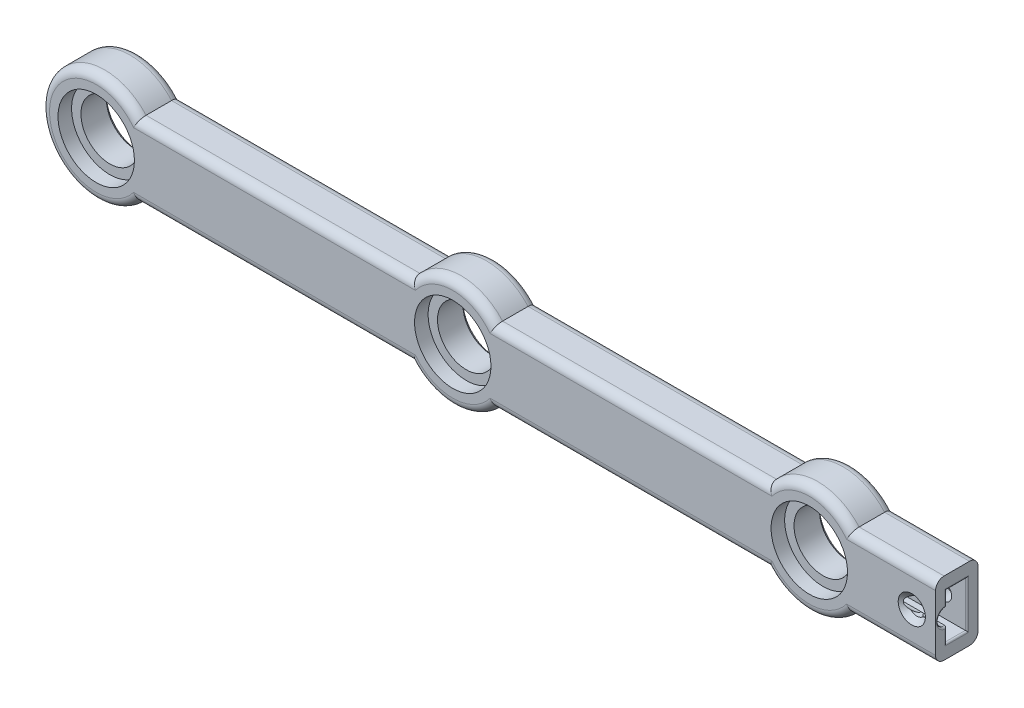
SolidWorks part; units mm, degrees
material "ABS"
ref_plane "Front Plane" through (0, 0, 0) normal (0, 0, 1) x (1, 0, 0)
ref_plane "Top Plane" through (0, 0, 0) normal (0, 1, 0) x (1, 0, 0)
ref_plane "Right Plane" through (0, 0, 0) normal (1, 0, 0) x (0, 0, -1)
sketch "Sketch1" plane through (0, 0, 0) normal (0, 0, 1) x (1, 0, 0)
  line L0 (-21, 0) -> (21, 0) construction
  line L1 (-18.5628, 2.15) -> (-2.4372, 2.15)
  line L2 (-18.5628, -2.15) -> (-2.4372, -2.15)
  line L3 (2.4372, -2.15) -> (18.5628, -2.15)
  line L4 (2.4372, 2.15) -> (18.5628, 2.15)
  line L5 (21, 0) -> (32.5393, 0) construction
  line L7 (23.4372, 2.15) -> (28.4372, 2.15)
  line L9 (23.4372, -2.15) -> (28.4372, -2.15)
  line L10 (28.4372, 2.15) -> (28.4372, -2.15)
  circle A0 centre (0, 0) radius 1.7
  circle A1 centre (-21, 0) radius 1.7
  circle A2 centre (21, 0) radius 1.7
  arc A3 (-18.5628, 2.15) -> (-18.5628, -2.15) centre (-21, 0) ccw
  arc A4 (-2.4372, -2.15) -> (2.4372, -2.15) centre (0, 0) ccw
  arc A5 (18.5628, -2.15) -> (23.4372, -2.15) centre (21, 0) ccw
  arc A6 (2.4372, 2.15) -> (-2.4372, 2.15) centre (0, 0) ccw
  arc A7 (23.4372, 2.15) -> (18.5628, 2.15) centre (21, 0) ccw
  dimension "D3" = 3.4
  dimension "D4" = 6.5
  dimension "D1" = 21
  dimension "D2" = 21
  dimension "D5" = 4.3
  dimension "D6" = 5
extrude "Boss-Extrude1" add sketch "Sketch1" along normal blind 2.5
sketch "Sketch2" plane through (0, 0, 2.5) normal (0, 0, 1) x (1, 0, 0)
  circle A0 centre (-21, 0) radius 2.25
  circle A1 centre (0, 0) radius 2.25
  circle A2 centre (21, 0) radius 2.25
  dimension "D1" = 4.5
extrude "Cut-Extrude1" cut sketch "Sketch2" against normal blind 0.8
chamfer "Chamfer1" distance 0.2 angle 45 3 edges at (-19.3, 0, 0) (1.7, 0, 0) (22.7, 0, 0)
fillet "Fillet1" radius 0.5 22 edges at (25.9372, 2.15, 0) (25.9372, -2.15, 0) (21, -3.25, 0) (10.5, -2.15, 0) (0, -3.25, 0) (-10.5, -2.15, 0) (21, 3.25, 0) (10.5, 2.15, 0) (0, 3.25, 0) (-10.5, 2.15, 0) (-24.25, 0, 0) (25.9372, -2.15, 2.5) (21, -3.25, 2.5) (10.5, -2.15, 2.5) (0, -3.25, 2.5) (-10.5, -2.15, 2.5) (25.9372, 2.15, 2.5) (21, 3.25, 2.5) (10.5, 2.15, 2.5) (0, 3.25, 2.5) (-10.5, 2.15, 2.5) (-24.25, 0, 2.5)
sketch "Sketch3" plane through (28.4372, 0, 0) normal (1, 0, 0) x (0, 0, -1)
  line L0 (-1.25, -2.15) -> (-1.25, 2.15) construction
  line L1 (-2, -2.15) -> (-0.5, -2.15) construction
  line L2 (-2, 2.15) -> (-0.5, 2.15) construction
  line L3 (-2.5, 0) -> (0, 0) construction
  line L4 (-2.5, -1.65) -> (-2.5, 1.65) construction
  line L5 (0, -1.65) -> (0, 1.65) construction
  line L6 (-1.85, -0.5) -> (-1.85, -1.35)
  line L7 (-1.85, 1.35) -> (-0.65, 1.35)
  line L8 (-1.85, 1.35) -> (-1.85, 0.5)
  line L9 (-1.85, -1.35) -> (-0.65, -1.35)
  line L10 (-0.65, 1.35) -> (-0.65, -1.35)
  line L11 (-1.85, 1.35) -> (-0.65, -1.35) construction
  line L12 (-1.85, -1.35) -> (-0.65, 1.35) construction
  line L13 (-1.85, 0.5) -> (-1.85, 0) construction
  arc A0 (-1.85, 0.5) -> (-1.85, -0.5) centre (-1.85, 0) ccw
  point P12 (-1.25, 0)
  dimension "D3" = 1
  dimension "D1" = 1.2
  dimension "D2" = 2.7
extrude "Cut-Extrude2" cut sketch "Sketch3" against normal blind 4
fillet "Fillet2" radius 0.1 6 edges at (28.4372, -0.925, 1.85) (28.4372, -1.35, 1.25) (28.4372, 0, 2.35) (28.4372, 0.925, 1.85) (28.4372, 0, 0.65) (28.4372, 1.35, 1.25)
sketch "Sketch4" plane through (0, 0, 2.5) normal (0, 0, 1) x (1, 0, 0)
  line L0 (28.4372, 0) -> (23.25, 0) construction
  line L1 (28.4372, -1.65) -> (28.4372, 1.65) construction
  circle A0 centre (21, 0) radius 2.25 construction
  circle A1 centre (27.0372, 0) radius 0.5
  dimension "D2" = 1
  dimension "D1" = 1.4
extrude "Cut-Extrude3" cut sketch "Sketch4" against normal through all
chamfer "Chamfer2" distance 0.3 angle 45 1 edges at (27.5372, 0, 2.5)
